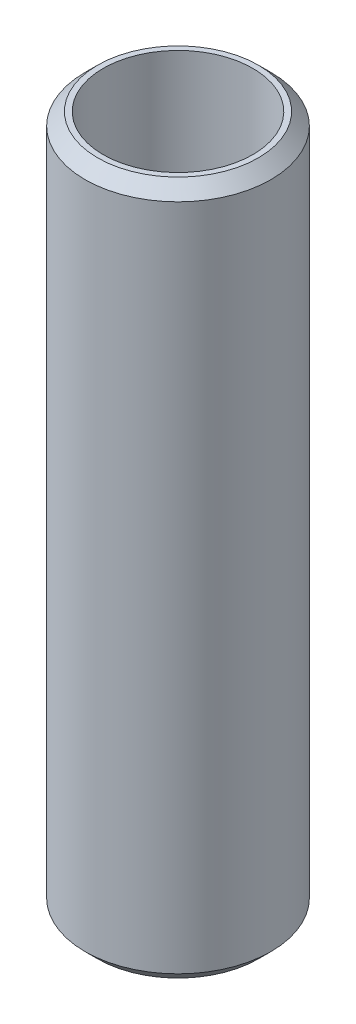
SolidWorks part; units mm, degrees
ref_plane "Front Plane" through (0, 0, 0) normal (0, 0, 1) x (1, 0, 0)
ref_plane "Top Plane" through (0, 0, 0) normal (0, 1, 0) x (1, 0, 0)
ref_plane "Right Plane" through (0, 0, 0) normal (1, 0, 0) x (0, 0, -1)
sketch "Sketch1" plane through (0, 0, 0) normal (0, 1, 0) x (1, 0, 0)
  circle A0 centre (0, 0) radius 27.5
  dimension "SHAFT_OD" = 55
extrude "Boss-Extrude1" add sketch "Sketch1" along normal blind 205.3011
sketch "Sketch2" plane through (0, 0, 0) normal (0, 1, 0) x (1, 0, 0)
  circle A0 centre (0, 0) radius 22.143
  dimension "BORE_D" = 44.286
extrude "Cut-Extrude1" cut sketch "Sketch2" along normal through all
chamfer "Chamfer1" distance 3.7179 angle 45 2 edges at (0, 205.3011, 27.5) (0, 0, 27.5)
